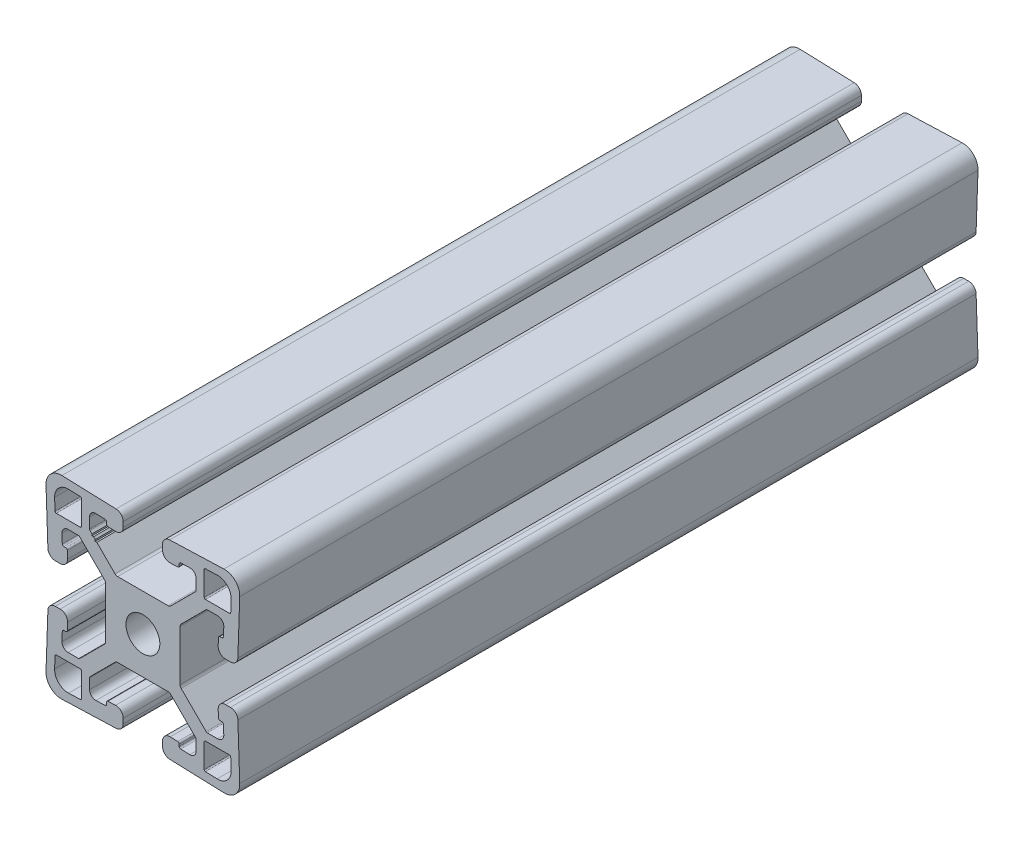
SolidWorks part; units mm, degrees
ref_plane "Front Plane" through (0, 0, 0) normal (0, 0, 1) x (1, 0, 0)
ref_plane "Top Plane" through (0, 0, 0) normal (0, 1, 0) x (1, 0, 0)
ref_plane "Right Plane" through (0, 0, 0) normal (1, 0, 0) x (0, 0, -1)
sketch "Sketch1" plane through (0, 0, 0) normal (0, 0, 1) x (1, 0, 0)
  line L0 (0, 0) -> (0, 20) construction
  line L1 (0, 0) -> (20, 0) construction
  line L2 (0, 0) -> (-20, 20) construction
  line L3 (-16.7142, 19.9981) -> (-5.5358, 19.6077)
  line L4 (-20, 20) -> (0, 20) construction
  line L5 (-4.064, 18.0836) -> (-4.064, 17.069)
  line L6 (-5.6422, 15.5449) -> (-7.1936, 15.5991)
  line L7 (-7.5, 15.9164) -> (-7.5, 16.3198)
  line L8 (-7.8064, 16.6371) -> (-9.6857, 16.7028)
  line L9 (-11, 15.4335) -> (-11, 13.2868)
  line L10 (0, 7.681) -> (-5.2101, 7.681)
  line L11 (-5.7489, 7.9042) -> (-10.907, 13.0623)
  line L12 (-7.9042, 5.7489) -> (-13.0623, 10.907)
  line L13 (-7.681, 0) -> (-7.681, 5.2101)
  line L14 (-15.4335, 11) -> (-13.2868, 11)
  line L15 (-16.6371, 7.8064) -> (-16.7028, 9.6857)
  line L16 (-15.9164, 7.5) -> (-16.3198, 7.5)
  line L17 (-15.5449, 5.6422) -> (-15.5991, 7.1936)
  line L18 (-18.0836, 4.064) -> (-17.069, 4.064)
  line L19 (-19.9981, 16.7142) -> (-19.6077, 5.5358)
  line L20 (-18.2207, 15.3309) -> (-18.1275, 12.661)
  line L21 (-15.3309, 18.2207) -> (-12.661, 18.1275)
  line L22 (-18.1275, 12.661) -> (-12.661, 12.661)
  line L23 (-12.661, 18.1275) -> (-12.661, 12.661)
  line L24 (0, 0) -> (-20, 0) construction
  line L25 (-20, 0) -> (0, 0) construction
  line L26 (0, 0) -> (0, -20) construction
  line L27 (-20, -20) -> (-20, 20) construction
  line L28 (0, 20) -> (20, 20) construction
  line L30 (-20, -20) -> (20, -20) construction
  arc A0 (-19.9981, 16.7142) -> (-16.7142, 19.9981) centre (-16.825, 16.825) cw
  arc A1 (-7.1936, 15.5991) -> (-7.5, 15.9164) centre (-7.1825, 15.9164) cw
  arc A2 (-7.5, 16.3198) -> (-7.8064, 16.6371) centre (-7.8175, 16.3198) ccw
  arc A3 (-9.6857, 16.7028) -> (-11, 15.4335) centre (-9.73, 15.4335) ccw
  arc A4 (-4.064, 17.069) -> (-5.6422, 15.5449) centre (-5.589, 17.069) cw
  arc A5 (-5.5358, 19.6077) -> (-4.064, 18.0836) centre (-5.589, 18.0836) cw
  arc A6 (-5.2101, 7.681) -> (-5.7489, 7.9042) centre (-5.2101, 8.443) cw
  arc A7 (-7.9042, 5.7489) -> (-7.681, 5.2101) centre (-8.443, 5.2101) cw
  arc A8 (-11, 13.2868) -> (-10.907, 13.0623) centre (-10.6825, 13.2868) ccw
  arc A9 (-18.0836, 4.064) -> (-19.6077, 5.5358) centre (-18.0836, 5.589) cw
  arc A10 (-15.5449, 5.6422) -> (-17.069, 4.064) centre (-17.069, 5.589) cw
  arc A11 (-15.9164, 7.5) -> (-15.5991, 7.1936) centre (-15.9164, 7.1825) cw
  arc A12 (-16.6371, 7.8064) -> (-16.3198, 7.5) centre (-16.3198, 7.8175) ccw
  arc A13 (-15.4335, 11) -> (-16.7028, 9.6857) centre (-15.4335, 9.73) ccw
  arc A14 (-13.0623, 10.907) -> (-13.2868, 11) centre (-13.2868, 10.6825) ccw
  arc A15 (-15.3309, 18.2207) -> (-18.2207, 15.3309) centre (-15.4284, 15.4284) ccw
  circle A16 centre (0, 0) radius 3.5
  point P26 (-7.5, 15.6098)
  point P29 (-7.5, 16.6264)
  point P32 (-11, 16.7487)
  point P35 (-4.064, 15.4898)
  point P38 (-4.064, 19.5563)
  point P42 (-5.5257, 7.681)
  point P45 (-7.681, 5.5257)
  point P48 (-11, 13.1553)
  point P51 (-19.5563, 4.064)
  point P54 (-15.4898, 4.064)
  point P57 (-15.6098, 7.5)
  point P60 (-16.6264, 7.5)
  point P63 (-16.7487, 11)
  point P66 (-13.1553, 11)
  point P80 (-20, 0)
  point P85 (0, -20)
  point P88 (0, -20)
  dimension "D11" = 3.175
  dimension "D14" = 1.27
  dimension "D16" = 1.525
  dimension "D15" = 0.762
  dimension "D21" = 2.794
  dimension "D4" = 0.3175
  dimension "Center Hole Diameter" = 7
  dimension "D1" = 45
  dimension "D2" = 2
  dimension "Rail Width" = 40
  dimension "T-Slot Width" = 8.128
  dimension "D6" = 3.048
  dimension "D10" = 3.048
  dimension "D13" = 1.728
  dimension "D8" = 22
  dimension "D18" = 1.661
  dimension "D19" = 7.339
  dimension "D20" = 7.339
  dimension "T-Slot Depth" = 12.319
  dimension "D9" = 4.064
  dimension "Rail Height1" = 40
  dimension "Rail Height" = 40
  dimension "D23" = 15.362
  dimension "D3" = 20
  dimension "D7" = 3.5
sketch "Sketch2" plane through (0, 0, 0) normal (1, 0, 0) x (0, 0, -1)
  line L0 (-76.2, 0) -> (76.2, 0)
  line L1 (-76.2, -20) -> (-76.2, 20) construction
  line L2 (0, 0) -> (0, 20) construction
  line L3 (0, 0) -> (0, 20) construction
  line L4 (76.2, -20) -> (76.2, 20) construction
  point P0 (-16.2, 0)
  point P3 (0, 0)
  point P7 (16.2, 0)
  point P11 (-76.2, 0)
  point P14 (76.2, 0)
  dimension "D1" = 60
  dimension "Length" = 152.4
sketch "Sketch3" plane through (0, 0, 0) normal (0, 0, 1) x (1, 0, 0)
  line L0 (-7.681, 0) -> (-7.681, 5.2101) construction
  line L1 (-7.9042, 5.7489) -> (-13.0623, 10.907) construction
  line L2 (-15.4335, 11) -> (-13.2868, 11) construction
  line L3 (-16.6371, 7.8064) -> (-16.7028, 9.6857) construction
  line L4 (-18.2207, 15.3309) -> (-18.1275, 12.661)
  line L5 (-18.1275, 12.661) -> (-12.661, 12.661)
  line L6 (-12.661, 12.661) -> (-12.661, 18.1275)
  line L7 (-12.661, 18.1275) -> (-15.3309, 18.2207)
  line L8 (-18.2207, 15.3309) -> (-18.136, 12.9061)
  line L9 (-17.8822, 12.661) -> (-12.915, 12.661)
  line L10 (-12.661, 12.915) -> (-12.661, 17.8822)
  line L11 (-12.9061, 18.136) -> (-15.3309, 18.2207)
  line L12 (-15.9164, 7.5) -> (-16.3198, 7.5) construction
  line L13 (-15.5449, 5.6422) -> (-15.5991, 7.1936) construction
  line L14 (-18.0836, 4.064) -> (-17.069, 4.064) construction
  line L15 (-19.9981, 16.7142) -> (-19.6077, 5.5358) construction
  line L16 (-16.7142, 19.9981) -> (-5.5358, 19.6077) construction
  line L17 (-4.064, 18.0836) -> (-4.064, 17.069) construction
  line L18 (-5.6422, 15.5449) -> (-7.1936, 15.5991) construction
  line L19 (-7.5, 15.9164) -> (-7.5, 16.3198) construction
  line L20 (-7.8064, 16.6371) -> (-9.6857, 16.7028) construction
  line L21 (-11, 15.4335) -> (-11, 13.2868) construction
  line L22 (-5.7489, 7.9042) -> (-10.907, 13.0623) construction
  line L23 (0, 7.681) -> (-5.2101, 7.681) construction
  line L24 (-7.681, 0) -> (-7.681, 5.2101)
  line L25 (-7.9042, 5.7489) -> (-13.0623, 10.907)
  line L26 (-15.4335, 11) -> (-13.2868, 11)
  line L27 (-16.6371, 7.8064) -> (-16.7028, 9.6857)
  line L28 (-15.9164, 7.5) -> (-16.3198, 7.5)
  line L29 (-15.5449, 5.6422) -> (-15.5991, 7.1936)
  line L30 (-18.0836, 4.064) -> (-17.069, 4.064)
  line L31 (-19.9981, 16.7142) -> (-19.6077, 5.5358)
  line L32 (-16.7142, 19.9981) -> (-5.5358, 19.6077)
  line L33 (-4.064, 18.0836) -> (-4.064, 17.069)
  line L34 (-5.6422, 15.5449) -> (-7.1936, 15.5991)
  line L35 (-7.5, 15.9164) -> (-7.5, 16.3198)
  line L36 (-7.8064, 16.6371) -> (-9.6857, 16.7028)
  line L37 (-11, 15.4335) -> (-11, 13.2868)
  line L38 (-5.7489, 7.9042) -> (-10.907, 13.0623)
  line L39 (0, 7.681) -> (-5.2101, 7.681)
  line L40 (-7.681, 0) -> (-3.5, 0)
  line L41 (0, 3.5) -> (0, 7.681)
  arc A0 (-7.681, 5.2101) -> (-7.9042, 5.7489) centre (-8.443, 5.2101) ccw construction
  circle A1 centre (0, 0) radius 3.5
  arc A2 (0, 3.5) -> (-3.5, 0) centre (0, 0) ccw
  arc A3 (-15.3309, 18.2207) -> (-18.2207, 15.3309) centre (-15.4284, 15.4284) ccw
  arc A4 (-15.3309, 18.2207) -> (-18.2207, 15.3309) centre (-15.4284, 15.4284) ccw
  arc A5 (-13.0623, 10.907) -> (-13.2868, 11) centre (-13.2868, 10.6825) ccw construction
  arc A6 (-15.4335, 11) -> (-16.7028, 9.6857) centre (-15.4335, 9.73) ccw construction
  arc A7 (-16.6371, 7.8064) -> (-16.3198, 7.5) centre (-16.3198, 7.8175) ccw construction
  arc A8 (-15.5991, 7.1936) -> (-15.9164, 7.5) centre (-15.9164, 7.1825) ccw construction
  arc A9 (-17.069, 4.064) -> (-15.5449, 5.6422) centre (-17.069, 5.589) ccw construction
  arc A10 (-19.6077, 5.5358) -> (-18.0836, 4.064) centre (-18.0836, 5.589) ccw construction
  arc A11 (-16.7142, 19.9981) -> (-19.9981, 16.7142) centre (-16.825, 16.825) ccw construction
  arc A12 (-4.064, 18.0836) -> (-5.5358, 19.6077) centre (-5.589, 18.0836) ccw construction
  arc A13 (-5.6422, 15.5449) -> (-4.064, 17.069) centre (-5.589, 17.069) ccw construction
  arc A14 (-7.5, 15.9164) -> (-7.1936, 15.5991) centre (-7.1825, 15.9164) ccw construction
  arc A15 (-7.5, 16.3198) -> (-7.8064, 16.6371) centre (-7.8175, 16.3198) ccw construction
  arc A16 (-9.6857, 16.7028) -> (-11, 15.4335) centre (-9.73, 15.4335) ccw construction
  arc A17 (-11, 13.2868) -> (-10.907, 13.0623) centre (-10.6825, 13.2868) ccw construction
  arc A18 (-5.7489, 7.9042) -> (-5.2101, 7.681) centre (-5.2101, 8.443) ccw construction
  arc A19 (-7.681, 5.2101) -> (-7.9042, 5.7489) centre (-8.443, 5.2101) ccw
  arc A20 (-13.0623, 10.907) -> (-13.2868, 11) centre (-13.2868, 10.6825) ccw
  arc A21 (-15.4335, 11) -> (-16.7028, 9.6857) centre (-15.4335, 9.73) ccw
  arc A22 (-16.6371, 7.8064) -> (-16.3198, 7.5) centre (-16.3198, 7.8175) ccw
  arc A23 (-15.5991, 7.1936) -> (-15.9164, 7.5) centre (-15.9164, 7.1825) ccw
  arc A24 (-17.069, 4.064) -> (-15.5449, 5.6422) centre (-17.069, 5.589) ccw
  arc A25 (-19.6077, 5.5358) -> (-18.0836, 4.064) centre (-18.0836, 5.589) ccw
  arc A26 (-16.7142, 19.9981) -> (-19.9981, 16.7142) centre (-16.825, 16.825) ccw
  arc A27 (-4.064, 18.0836) -> (-5.5358, 19.6077) centre (-5.589, 18.0836) ccw
  arc A28 (-5.6422, 15.5449) -> (-4.064, 17.069) centre (-5.589, 17.069) ccw
  arc A29 (-7.5, 15.9164) -> (-7.1936, 15.5991) centre (-7.1825, 15.9164) ccw
  arc A30 (-7.5, 16.3198) -> (-7.8064, 16.6371) centre (-7.8175, 16.3198) ccw
  arc A31 (-9.6857, 16.7028) -> (-11, 15.4335) centre (-9.73, 15.4335) ccw
  arc A32 (-11, 13.2868) -> (-10.907, 13.0623) centre (-10.6825, 13.2868) ccw
  arc A33 (-5.7489, 7.9042) -> (-5.2101, 7.681) centre (-5.2101, 8.443) ccw
  arc A36 (-12.661, 17.8822) -> (-12.9061, 18.136) centre (-12.915, 17.8822) ccw
  arc A37 (-12.915, 12.661) -> (-12.661, 12.915) centre (-12.915, 12.915) ccw
  arc A38 (-18.136, 12.9061) -> (-17.8822, 12.661) centre (-17.8822, 12.915) ccw
  dimension "D3" = 0.254
  dimension "D1" = 0
  dimension "D2" = 0
extrude "Boss-Extrude1" add sketch "Sketch3" along normal mid plane 152.4
pattern_circular "CirPattern1" count 4 over 360 about axis through (0, 0, 76.2) along (0, 0, -1) of "Boss-Extrude1"
sketch "Sketch4" plane through (0, 0, 0) normal (0, 0, 1) x (1, 0, 0)
  line L1 (-10.5057, 12.661) -> (-9.5057, 12.661)
  line L8 (-5.7489, 7.9042) -> (-10.907, 13.0623) construction
  line L9 (-9.5057, 12.661) -> (-9.5057, 11.661)
  line L10 (-9.5057, 11.661) -> (-9.8391, 11.661)
  line L12 (-10.1724, 12.3277) -> (-9.8391, 11.9943)
  line L20 (-9.8391, 11.9943) -> (-9.8391, 12.3277) construction
  line L22 (-9.8391, 11.661) -> (-9.8391, 11.9943)
  line L23 (-9.8391, 12.3277) -> (-10.1724, 12.3277) construction
  line L25 (-10.1724, 12.3277) -> (-10.5057, 12.3277)
  line L26 (-10.5057, 12.3277) -> (-10.5057, 12.661)
  line L27 (-17.8822, 12.661) -> (-12.915, 12.661) construction
  dimension "D2" = 1
extrude "Cut-Extrude1" cut sketch "Sketch4" against normal through all both and the other way through all
ref_plane "Contact Plane 1" through (0, 20, 0) normal (0, 1, 0) x (1, 0, 0)
ref_plane "Contact Plane 2" through (20, 0, 0) normal (1, 0, 0) x (0, 0, -1)
ref_plane "Contact Plane 3" through (0, -20, 0) normal (0, -1, 0) x (-1, 0, 0)
ref_plane "Contact Plane 4" through (-20, 0, 0) normal (-1, 0, 0) x (0, 0, 1)
equation "\"D1@Sketch2\"=\"Rail Width@Sketch1\"*1.5"
equation "\"D1@Boss-Extrude1\"=\"Length@Sketch2\""
equation "\"ShaftDiameter\"= 12mm"
equation "\"PendulumDiameter\"=12mm"
equation "\"PendulumLength\"= 140mm"
equation "\"EncoderOuterDiameter\"=1.5"
equation "\"EncoderShaftDiameter\"= 6mm"
equation "\"EncoderShaftLength\"=15mm+.5in+3mm"
equation "\"PendulumHolderangle\"=60"
equation "\"PendulumholderBottomHeight\"= 75"
equation "\"PendulumholderBottomWidth\"= 75"
equation "\"PendulumholderHeight\"=25"
equation "\"BearingOutsideDiameter\"=21mm"
equation "\"PendulumHolderWidth\"= 100mm"
equation "\"ShaftHeightFromTSlot\"= 100mm"
equation "\"BearingThickness\"= 5mm"
equation "\"SlipRingOuterDiameter\"=56mm"
equation "\"SlipringBigThickness\"=25mm"
equation "\"SlipringSmallThickness\"=8.5mm"
equation "\"Tol\"=2mm"
equation "\"ScrewHole\"= 5mm"
equation "\"Tframwidth\"= 40mm"
equation "\"TFrameheight\"= 12in"
equation "\"Tframetotalwidth\"= 2ft"
equation "\"TFramethickness\"= 6in"
equation "\"Length@Sketch2\"=\"TFramethickness\""
